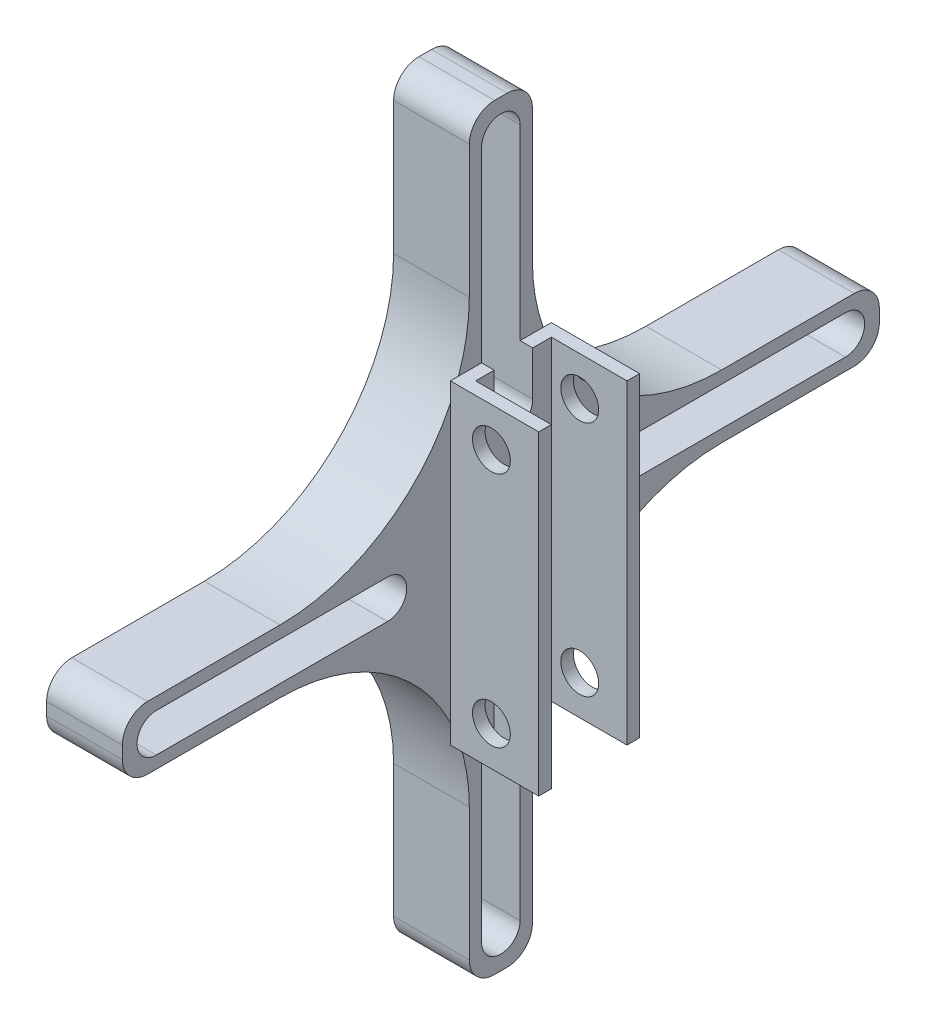
SolidWorks part; units mm, degrees
note: The reader was unsure of these and kept them because the rebuilt part matched: shared geometry of "Sketch3<4>", "Sketch3<5>".
ref_plane "Front Plane" through (0, 0, 0) normal (0, 0, 1) x (1, 0, 0)
ref_plane "Top Plane" through (0, 0, 0) normal (0, 1, 0) x (1, 0, 0)
ref_plane "Right Plane" through (0, 0, 0) normal (1, 0, 0) x (0, 0, -1)
sketch "Sketch1" plane through (0, 0, 0) normal (0, 1, 0) x (1, 0, 0)
  line L0 (-3, 3) -> (3, -3) construction
  line L1 (-3, 3) -> (3, 3)
  line L2 (-3, 3) -> (-3, -3)
  line L3 (-3, -3) -> (3, -3)
  line L4 (3, 4) -> (3, 3)
  line L5 (-4, 4) -> (3, 4)
  line L7 (-4, -4) -> (3, -4)
  line L8 (-4, 4) -> (-4, -4)
  line L9 (3, 3) -> (3, -3) construction
  line L10 (-4, 4) -> (4, 4) construction
  line L11 (4, 4) -> (4, -4) construction
  line L12 (-4, -4) -> (4, -4) construction
  line L13 (3, -3) -> (3, -4)
  dimension "D1" = 6
  dimension "D2" = 6
  dimension "D3" = 1
extrude "Boss-Extrude1" add sketch "Sketch1" along normal blind 25 contours L5 L4 L1 L2 L3 L13 L7 L8
sketch "Sketch2" plane through (0, 0, 4) normal (0, 0, 1) x (1, 0, 0)
  line L0 (-0.75, 21.895) -> (-0.75, 3.105) construction
  line L1 (-4, 12.5) -> (3, 12.5) construction
  line L2 (-4, 25) -> (-4, 0) construction
  line L3 (3, 25) -> (3, 0) construction
  circle A0 centre (-0.75, 3.105) radius 1.5
  circle A1 centre (-0.75, 21.895) radius 1.5
  point P10 (-0.75, 12.5)
  point P11 (0, 0)
  dimension "D1" = 3
  dimension "D2" = 18.79
  dimension "D3" = 3.25
extrude "Cut-Extrude1" cut sketch "Sketch2" against normal blind 100
sketch "Sketch3" plane through (-4, 0, 0) normal (-1, 0, 0) x (0, 0, 1)
  line L0 (-4, 12.5) -> (4, 12.5) construction
  line L1 (-4, 25) -> (-4, 0) construction
  line L2 (4, 25) -> (4, 0) construction
  line L3 (-2.5, 42.5) -> (2.5, -17.5) construction
  line L4 (-0.5, 42.5) -> (0.5, 42.5)
  line L5 (-2.5, 40.5) -> (-2.5, 30)
  line L6 (-0.5, -17.5) -> (0.5, -17.5)
  line L7 (2.5, 40.5) -> (2.5, 30)
  line L8 (-30, 15) -> (30, 10) construction
  line L9 (-28, 15) -> (-17.5, 15)
  line L10 (-30, 13) -> (-30, 12)
  line L11 (-28, 10) -> (-17.5, 10)
  line L12 (30, 13) -> (30, 12)
  line L13 (17.5, 15) -> (28, 15)
  line L14 (-2.5, 12.7083) -> (-2.5, 12.5)
  line L15 (-2.5, -5) -> (-2.5, -15.5)
  line L16 (17.5, 10) -> (28, 10)
  line L17 (2.5, -5) -> (2.5, -15.5)
  line L18 (2.5, 12.5) -> (2.5, 12.2917)
  line L19 (-27.3128, 12.5) -> (-8.988, 12.5) construction
  line L20 (-27.3128, 14.025) -> (-8.988, 14.025)
  line L21 (-27.3128, 10.975) -> (-8.988, 10.975)
  line L22 (0, 12.5) -> (-2.5, 15) construction
  line L23 (0, 12.5) -> (0, 25) construction
  line L24 (-4, 25) -> (4, 25) construction
  line L25 (27.3128, 12.5) -> (8.988, 12.5) construction
  line L26 (27.3128, 14.025) -> (8.988, 14.025)
  line L27 (27.3128, 10.975) -> (8.988, 10.975)
  line L28 (0, -14.8128) -> (0, 3.512) construction
  line L29 (-1.525, -14.8128) -> (-1.525, 3.512)
  line L30 (1.525, -14.8128) -> (1.525, 3.512)
  line L31 (0, 39.8128) -> (0, 21.488) construction
  line L32 (-1.525, 39.8128) -> (-1.525, 21.488)
  line L33 (1.525, 39.8128) -> (1.525, 21.488)
  arc A0 (-27.3128, 14.025) -> (-27.3128, 10.975) centre (-27.3128, 12.5) ccw
  arc A1 (-8.988, 10.975) -> (-8.988, 14.025) centre (-8.988, 12.5) ccw
  arc A2 (27.3128, 14.025) -> (27.3128, 10.975) centre (27.3128, 12.5) cw
  arc A3 (8.988, 10.975) -> (8.988, 14.025) centre (8.988, 12.5) cw
  arc A4 (-1.525, -14.8128) -> (1.525, -14.8128) centre (0, -14.8128) ccw
  arc A5 (1.525, 3.512) -> (-1.525, 3.512) centre (0, 3.512) ccw
  arc A6 (-1.525, 39.8128) -> (1.525, 39.8128) centre (0, 39.8128) cw
  arc A7 (1.525, 21.488) -> (-1.525, 21.488) centre (0, 21.488) cw
  arc A8 (-30, 12) -> (-28, 10) centre (-28, 12) ccw
  arc A9 (-28, 15) -> (-30, 13) centre (-28, 13) ccw
  arc A10 (28, 10) -> (30, 12) centre (28, 12) ccw
  arc A11 (28, 15) -> (30, 13) centre (28, 13) cw
  arc A12 (0.5, -17.5) -> (2.5, -15.5) centre (0.5, -15.5) ccw
  arc A13 (-2.5, -15.5) -> (-0.5, -17.5) centre (-0.5, -15.5) ccw
  arc A14 (0.5, 42.5) -> (2.5, 40.5) centre (0.5, 40.5) cw
  arc A15 (-0.5, 42.5) -> (-2.5, 40.5) centre (-0.5, 40.5) ccw
  arc A16 (-2.5, -5) -> (-17.5, 10) centre (-17.5, -5) ccw
  arc A17 (17.5, 10) -> (2.5, -5) centre (17.5, -5) ccw
  arc A18 (17.5, 15) -> (2.5, 30) centre (17.5, 30) cw
  arc A19 (-17.5, 15) -> (-2.5, 30) centre (-17.5, 30) ccw
  point P6 (0, 12.5)
  point P15 (0, 12.5)
  point P26 (-18.1504, 12.5)
  point P37 (18.1504, 12.5)
  point P44 (0, -5.6504)
  point P51 (0, 30.6504)
  point P73 (2.5, 42.5)
  point P81 (2.5, 10)
  dimension "D3" = 2
  dimension "D4" = 15
  dimension "D1" = 5
  dimension "D2" = 60
extrude "Boss-Extrude2" add sketch "Sketch3" along normal blind 6
extrude "Cut-Extrude2" cut sketch "Sketch3<4>" against normal blind 6 contours L29 A5 L30 A4
sketch "Sketch3<4>" plane through (-4, 0, 0) normal (-1, 0, 0) x (0, 0, 1) same geometry as "Sketch3"
extrude "Cut-Extrude3" cut sketch "Sketch3<5>" against normal blind 6 contours L32 A7 L33 A6
sketch "Sketch3<5>" plane through (-4, 0, 0) normal (-1, 0, 0) x (0, 0, 1) same geometry as "Sketch3"
sketch "Sketch6" plane through (-10, 0, 0) normal (-1, 0, 0) x (0, 0, 1)
  circle A0 centre (0, 12.5) radius 2
  point P2 (0, 0)
  dimension "D2" = 4
  dimension "D1" = 12.5
extrude "Cut-Extrude4" cut sketch "Sketch6" against normal blind 60
